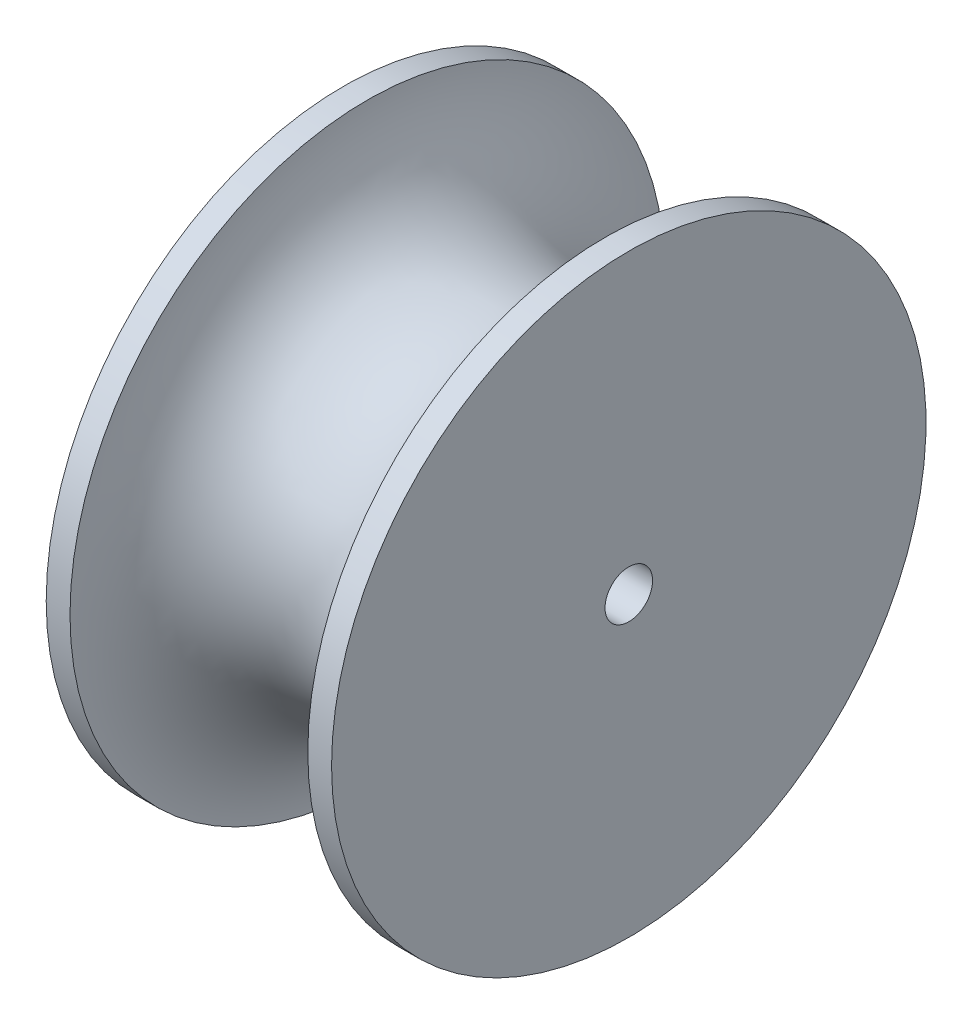
SolidWorks part; units mm, degrees
ref_plane "Front Plane" through (0, 0, 0) normal (0, 0, 1) x (1, 0, 0)
ref_plane "Top Plane" through (0, 0, 0) normal (0, 1, 0) x (1, 0, 0)
ref_plane "Right Plane" through (0, 0, 0) normal (1, 0, 0) x (0, 0, -1)
sketch "Sketch1" plane through (0, 0, 0) normal (0, 0, 1) x (1, 0, 0)
  line L3 (-10, -12.5) -> (10, -12.5)
  line L5 (-10, 12.5) -> (10, -12.5) construction
  line L6 (-10, -12.5) -> (10, 12.5) construction
  line L7 (10, 12.5) -> (12, 12.5)
  line L9 (10, -12.5) -> (12, -12.5)
  line L10 (12, 12.5) -> (12, -12.5)
  line L11 (-10, 12.5) -> (-12, 12.5)
  line L13 (-10, -12.5) -> (-12, -12.5)
  line L14 (-12, 12.5) -> (-12, -12.5)
  arc A0 (-10, 12.5) -> (10, 12.5) centre (0, 12.5) ccw
  point P0 (0, 0)
  dimension "D1" = 25
  dimension "D2" = 20
  dimension "D3" = 2
revolve "Revolve1" add sketch "Sketch1" angle 360 about L3
sketch "Sketch2" plane through (12, 0, 0) normal (1, 0, 0) x (0, 0, -1)
  line L0 (0, 12.5) -> (0, -37.5) construction
  circle A0 centre (0, -12.5) radius 25 construction
  circle A1 centre (0, -12.5) radius 2
  dimension "D1" = 4
extrude "Cut-Extrude1" cut sketch "Sketch2" against normal through all
